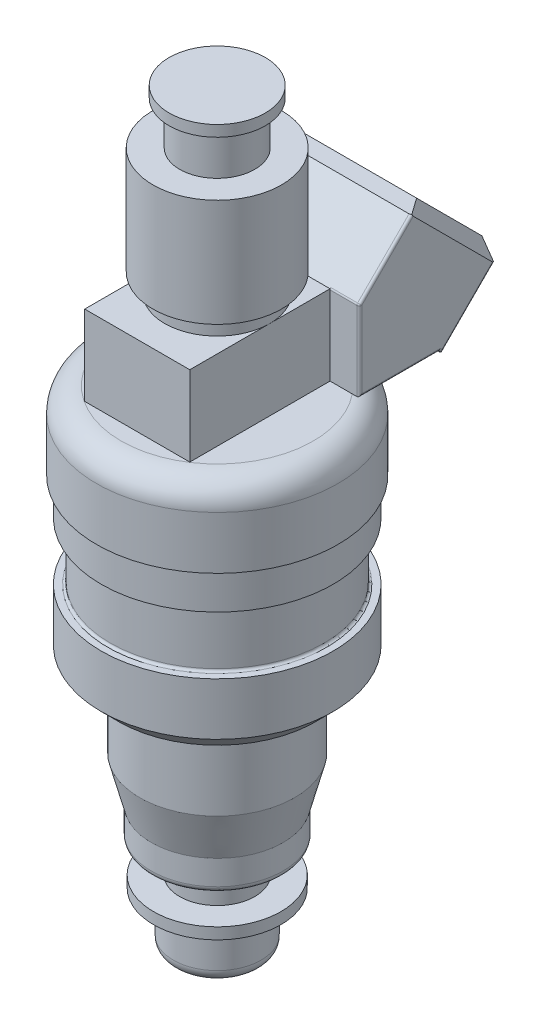
SolidWorks part; units mm, degrees
ref_plane "Front Plane" through (0, 0, 0) normal (0, 0, 1) x (1, 0, 0)
ref_plane "Top Plane" through (0, 0, 0) normal (0, 1, 0) x (1, 0, 0)
ref_plane "Right Plane" through (0, 0, 0) normal (1, 0, 0) x (0, 0, -1)
sketch "Sketch1" plane through (0, 0, 0) normal (0, 0, 1) x (1, 0, 0)
  line L0 (0, 0) -> (3.2639, 0)
  line L1 (4.5339, 1.27) -> (4.5339, 5.207)
  line L2 (4.7879, 5.461) -> (6.5786, 5.461)
  line L3 (0, 0) -> (0, 77.216)
  line L4 (6.5786, 5.461) -> (6.5786, 6.6294)
  line L5 (6.5786, 6.6294) -> (3.8862, 6.6294)
  line L6 (3.8862, 6.6294) -> (3.8862, 9.7282)
  line L7 (3.8862, 9.7282) -> (6.1595, 9.7282)
  line L8 (6.7945, 10.3632) -> (6.7945, 12.9032)
  line L9 (0, 77.216) -> (4.9657, 77.216)
  line L10 (8.001, 17.5307) -> (8.001, 24.13)
  line L11 (9.271, 25.4) -> (10.1673, 25.4)
  line L12 (10.1673, 25.4) -> (11.9634, 27.1961)
  line L13 (11.9634, 27.1961) -> (11.9634, 32.6063)
  line L14 (11.9634, 32.6063) -> (11.2903, 32.6063)
  line L15 (11.0363, 32.8603) -> (11.0363, 38.3213)
  line L16 (11.2903, 38.5753) -> (11.9634, 38.5753)
  line L17 (11.9634, 38.5753) -> (11.9634, 42.3853)
  line L18 (6.7945, 12.9032) -> (8.001, 17.5307)
  line L19 (4.9657, 77.216) -> (4.9657, 76.073)
  line L20 (4.9657, 76.073) -> (3.8735, 76.073)
  line L21 (3.8735, 76.073) -> (3.8735, 71.628)
  line L22 (3.8735, 71.628) -> (6.6421, 71.628)
  line L23 (6.6421, 71.628) -> (6.6421, 60.5282)
  line L24 (6.6421, 60.5282) -> (5.4229, 60.5282)
  line L25 (5.4229, 60.5282) -> (5.4229, 50.3682)
  line L26 (11.9634, 42.3853) -> (12.4587, 42.3853)
  line L27 (12.4587, 42.3853) -> (12.4587, 47.8282)
  line L28 (9.9187, 50.3682) -> (5.4229, 50.3682)
  arc A0 (3.2639, 0) -> (4.5339, 1.27) centre (3.2639, 1.27) ccw
  arc A1 (4.5339, 5.207) -> (4.7879, 5.461) centre (4.7879, 5.207) cw
  arc A2 (11.2903, 32.6063) -> (11.0363, 32.8603) centre (11.2903, 32.8603) cw
  arc A3 (11.0363, 38.3213) -> (11.2903, 38.5753) centre (11.2903, 38.3213) cw
  arc A4 (8.001, 24.13) -> (9.271, 25.4) centre (9.271, 24.13) cw
  arc A5 (6.1595, 9.7282) -> (6.7945, 10.3632) centre (6.1595, 10.3632) ccw
  arc A6 (12.4587, 47.8282) -> (9.9187, 50.3682) centre (9.9187, 47.8282) ccw
  point P12 (4.5339, 0)
  point P15 (4.5339, 5.461)
  point P32 (8.001, 25.4)
  point P35 (6.7945, 9.7282)
  dimension "D7" = 1.27
  dimension "D8" = 0.254
  dimension "D16" = 0.254
  dimension "D17" = 1.27
  dimension "D18" = 0.635
  dimension "D30" = 2.54
  dimension "D1" = 4.5339
  dimension "D2" = 5.461
  dimension "D3" = 6.5786
  dimension "D4" = 1.1684
  dimension "D5" = 3.8862
  dimension "D6" = 3.0988
  dimension "D9" = 6.7945
  dimension "D10" = 3.175
  dimension "D11" = 8.001
  dimension "D12" = 135
  dimension "D13" = 11.9634
  dimension "D14" = 5.4102
  dimension "D15" = 11.0363
  dimension "D19" = 5.969
  dimension "D20" = 77.216
  dimension "D21" = 4.9657
  dimension "D22" = 1.143
  dimension "D23" = 4.445
  dimension "D24" = 3.8735
  dimension "D25" = 6.6421
  dimension "D26" = 11.0998
  dimension "D27" = 10.16
  dimension "D28" = 3.81
  dimension "D29" = 5.4229
  dimension "D31" = 12.4587
  dimension "D32" = 2.54
  dimension "D33" = 25.4
revolve "Revolve1" add sketch "Sketch1" angle 360 about L3
sketch "Sketch2" plane through (0, 0, 0) normal (0, 0, 1) x (1, 0, 0)
  line L0 (5.4229, 50.3682) -> (5.4229, 60.5282) construction
  line L1 (-5.4229, 50.3682) -> (5.4229, 50.3682)
  line L2 (-5.4229, 50.3682) -> (-5.4229, 58.6232)
  line L3 (-5.4229, 58.6232) -> (5.4229, 58.6232)
  line L4 (5.4229, 50.3682) -> (5.4229, 58.6232)
  dimension "D1" = 8.255
extrude "Extrude1" add sketch "Sketch2" along normal blind 8.255 and the other way blind 6.223
ref_plane "Plane1" through (0, 32.4231, -32.4231) normal (0, 0.7071, -0.7071) x (-1, 0, 0)
sketch "Sketch3" plane through (0, 32.4231, -32.4231) normal (0, 0.7071, -0.7071) x (-1, 0, 0)
  line L0 (-5.4229, 37.0525) -> (5.4229, 37.0525) construction
  line L1 (-8.4455, 37.0525) -> (8.4455, 37.0525)
  line L2 (-8.4455, 37.0525) -> (-8.4455, 24.9875)
  line L3 (-8.4455, 24.9875) -> (8.4455, 24.9875)
  line L4 (8.4455, 37.0525) -> (8.4455, 24.9875)
  point P7 (0, 37.0525)
  point P9 (0, 37.0525)
  dimension "D1" = 16.891
  dimension "D2" = 12.065
extrude "Extrude2" add sketch "Sketch3" along normal blind 8.89 separate body
sketch "Sketch4" plane through (0, 0, -6.223) normal (0, 0, -1) x (-1, 0, 0)
  line L0 (9.9187, 50.3682) -> (-9.9187, 50.3682) construction
  line L1 (-8.4455, 58.6232) -> (8.4455, 58.6232)
  line L2 (-8.4455, 58.6232) -> (-8.4455, 50.3682)
  line L3 (-8.4455, 50.3682) -> (8.4455, 50.3682)
  line L4 (8.4455, 58.6232) -> (8.4455, 50.3682)
  line L5 (8.4455, 50.092) -> (8.4455, 58.6232) construction
extrude "Extrude3" add sketch "Sketch4" along normal up to surface up to face at (0, 54.3576, -10.4886)
chamfer "Chamfer1" distance 1.27 angle 45 4 edges at (8.4455, 60.6438, -16.7748) (0, 64.9094, -12.5092) (-8.4455, 60.6438, -16.7748) (0, 56.3781, -21.0404)
fillet "Fillet5" radius 0.254 12 edges at (8.4455, 61.3173, -8.9171) (8.4455, 54.4957, -6.223) (-8.4455, 54.4957, -6.223) (-8.4455, 61.3173, -8.9171) (-8.4455, 52.786, -17.4483) (8.4455, 52.786, -17.4483)
ref_axis "Axis1" through (0, 81.0768, 0) along (0, -1, 0)
